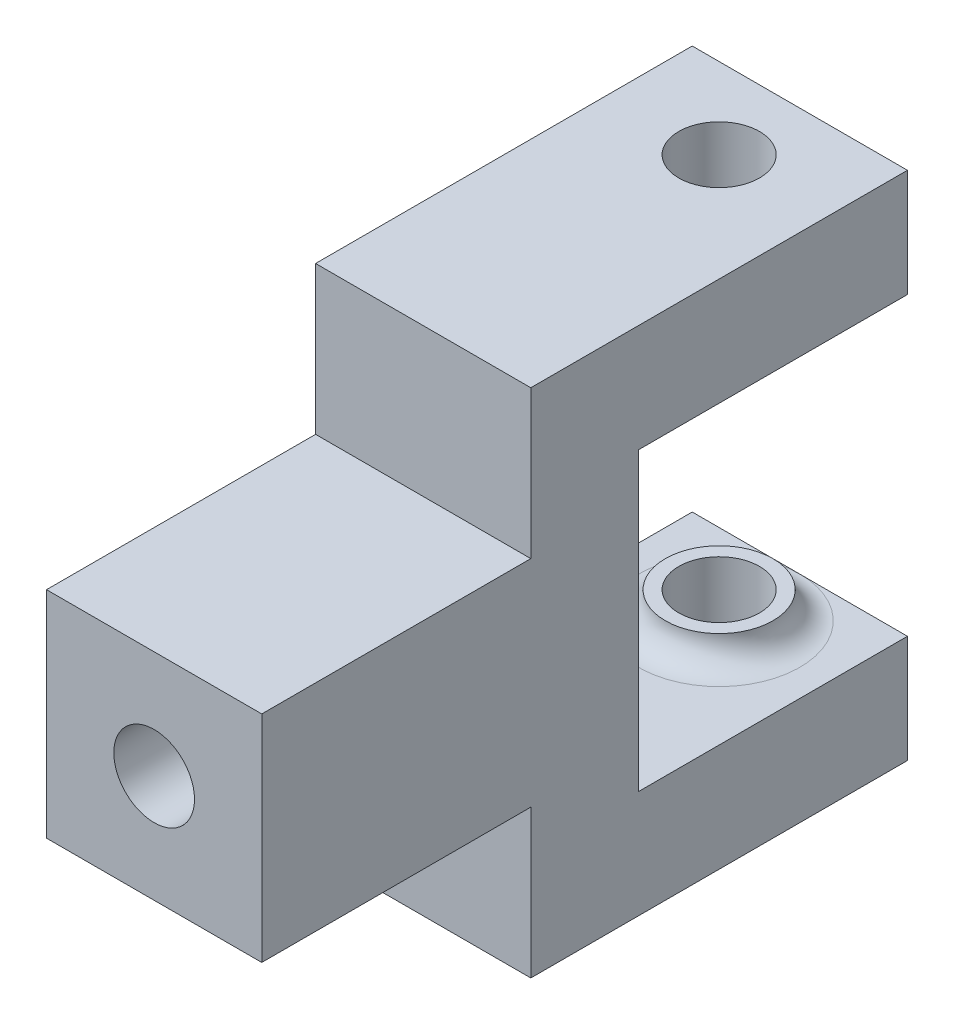
SolidWorks part; units mm, degrees
ref_plane "Спереди" through (0, 0, 0) normal (0, 0, 1) x (1, 0, 0)
ref_plane "Сверху" through (0, 0, 0) normal (0, 1, 0) x (1, 0, 0)
ref_plane "Справа" through (0, 0, 0) normal (1, 0, 0) x (0, 0, -1)
sketch "Эскиз3" plane through (0, 0, 0) normal (1, 0, 0) x (0, 0, -1)
  line L0 (0, 0) -> (14, 0)
  line L1 (14, 0) -> (14, 4)
  line L2 (14, 4) -> (4, 4)
  line L3 (4, 4) -> (4, 15)
  line L4 (4, 15) -> (14, 15)
  line L5 (14, 15) -> (14, 19)
  line L6 (14, 19) -> (0, 19)
  line L7 (0, 19) -> (0, 0)
  dimension "D1" = 4
  dimension "D2" = 4
  dimension "D3" = 11
  dimension "D4" = 10
  dimension "D5" = 4
  dimension "D6" = 14
extrude "Бобышка-Вытянуть1" add sketch "Эскиз3" along normal blind 8
sketch "Эскиз4" plane through (0, 19, 0) normal (0, 1, 0) x (1, 0, 0)
  line L0 (4, 14) -> (4, 0) construction
  line L1 (8, 14) -> (0, 14) construction
  line L2 (8, 0) -> (0, 0) construction
  circle A0 centre (4, 11) radius 1.5
  dimension "D2" = 3
  dimension "D1" = 3
extrude "Вырез-Вытянуть1" cut sketch "Эскиз4" against normal up to surface (19 mm away) up to face at (4, 0, -7)
sketch "Эскиз5" plane through (0, 4, 0) normal (0, 1, 0) x (1, 0, 0)
  circle A0 centre (4, 11) radius 2
  circle A1 centre (4, 11) radius 1.5
  dimension "D1" = 4
  dimension "D2" = 3
extrude "Бобышка-Вытянуть2" add sketch "Эскиз5" along normal blind 1
sketch "Эскиз6" plane through (0, 15, 0) normal (0, -1, 0) x (-1, 0, 0)
  circle A0 centre (-4, 11) radius 2
  circle A1 centre (-4, 11) radius 1.5
  dimension "D1" = 4
  dimension "D2" = 3
extrude "Бобышка-Вытянуть3" add sketch "Эскиз6" along normal blind 1
fillet "Скругление1" radius 1 1 edges at (4, 4, -13)
fillet "Скругление2" radius 1 1 edges at (4, 15, -9)
sketch "Эскиз10" plane through (0, 0, 0) normal (0, 0, 1) x (1, 0, 0)
  line L0 (8, 13.5) -> (0, 13.5)
  line L1 (8, 19) -> (8, 0) construction
  line L2 (0, 19) -> (0, 0) construction
  line L3 (0, 13.5) -> (0, 5.5)
  line L4 (0, 5.5) -> (8, 5.5)
  line L5 (8, 5.5) -> (8, 13.5)
  line L6 (4, 19) -> (4, 0) construction
  line L7 (8, 19) -> (0, 19) construction
  line L8 (8, 0) -> (0, 0) construction
  line L9 (2.2308, 9.5) -> (5.8965, 9.5) construction
  dimension "D1" = 8
extrude "Бобышка-Вытянуть5" add sketch "Эскиз10" along normal blind 10
sketch "Эскиз7" plane through (0, 0, -4) normal (0, 0, -1) x (-1, 0, 0)
  line L0 (-8, 9.5) -> (0, 9.5) construction
  line L1 (-8, 4) -> (-8, 15) construction
  line L2 (0, 4) -> (0, 15) construction
  line L3 (-4, 15) -> (-4, 4) construction
  line L4 (-8, 15) -> (0, 15) construction
  line L5 (-8, 4) -> (0, 4) construction
  circle A0 centre (-4, 9.5) radius 1.5
  dimension "D1" = 3
extrude "Вырез-Вытянуть2" cut sketch "Эскиз7" against normal up to surface (14 mm away) up to face at (4, 9.5, 10)
sketch "Эскиз9" plane through (0, 0, -4) normal (0, 0, -1) x (-1, 0, 0)
  line L1 (-1.2641, 11.1119) -> (-4.028, 12.6753)
  line L2 (-4.028, 12.6753) -> (-6.7639, 11.0634)
  line L3 (-6.7639, 11.0634) -> (-6.7359, 7.8881)
  line L4 (-6.7359, 7.8881) -> (-3.972, 6.3247)
  line L5 (-3.972, 6.3247) -> (-1.2361, 7.9366)
  line L6 (-1.2361, 7.9366) -> (-1.2641, 11.1119)
  circle A0 centre (-4, 9.5) radius 2.75 construction
  dimension "D1" = 5.5
extrude "Вырез-Вытянуть3" cut sketch "Эскиз9" against normal offset from surface (10 mm away) 4 up to face at (5.5, 9.5, 10)
